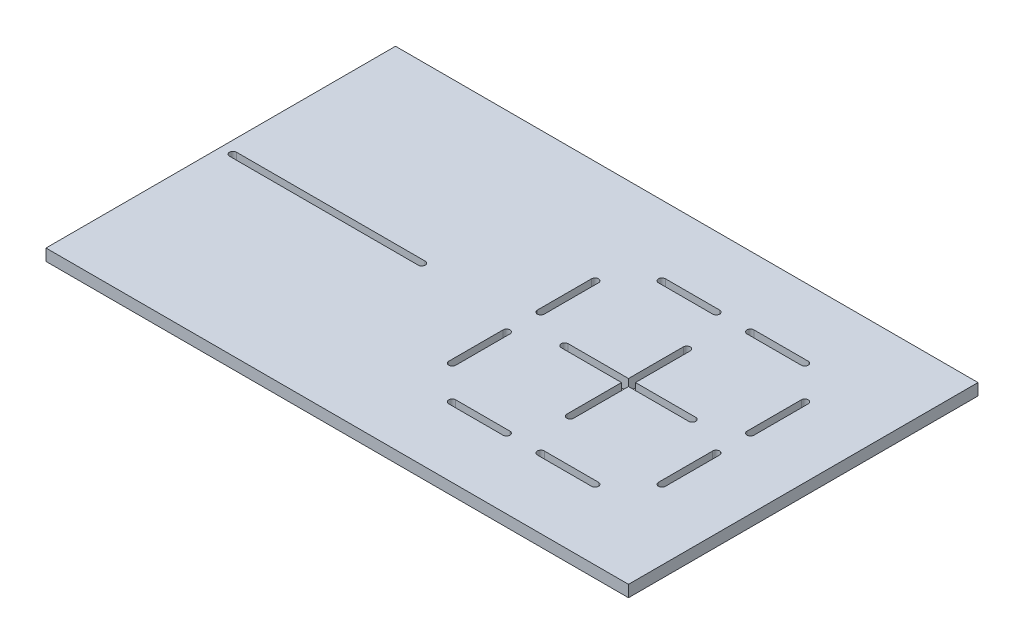
SolidWorks part; units mm, degrees
ref_plane "Front Plane" through (0, 0, 0) normal (0, 0, 1) x (1, 0, 0)
ref_plane "Top Plane" through (0, 0, 0) normal (0, 1, 0) x (1, 0, 0)
ref_plane "Right Plane" through (0, 0, 0) normal (1, 0, 0) x (0, 0, -1)
sketch "Sketch1" plane through (0, 0, 0) normal (0, 1, 0) x (1, 0, 0)
  line L1 (-54.3842, 257.5375) -> (445.6158, 257.5375)
  line L2 (-54.3842, 257.5375) -> (-54.3842, -42.4625)
  line L3 (-54.3842, -42.4625) -> (445.6158, -42.4625)
  line L4 (445.6158, 257.5375) -> (445.6158, -42.4625)
extrude "Boss-Extrude1" add sketch "Sketch1" along normal blind 10
sketch "Sketch2" plane through (0, 10, 0) normal (0, 1, 0) x (1, 0, 0)
  line L0 (-54.3842, 107.5375) -> (445.6158, 107.5375) construction
  line L1 (-54.3842, 257.5375) -> (-54.3842, -42.4625) construction
  line L2 (445.6158, -42.4625) -> (445.6158, 257.5375) construction
  line L3 (295.6158, 257.5375) -> (295.6158, -42.4625) construction
  line L4 (445.6158, 257.5375) -> (-54.3842, 257.5375) construction
  line L5 (-54.3842, -42.4625) -> (445.6158, -42.4625) construction
  line L6 (205.6158, 168.8297) -> (205.6158, 122.2426) construction
  line L7 (208.6158, 168.8297) -> (208.6158, 122.2426)
  line L8 (202.6158, 168.8297) -> (202.6158, 122.2426)
  line L9 (205.6158, 46.2453) -> (205.6158, 92.8323) construction
  line L10 (208.6158, 46.2453) -> (208.6158, 92.8323)
  line L11 (202.6158, 46.2453) -> (202.6158, 92.8323)
  line L12 (356.9081, 197.5375) -> (310.321, 197.5375) construction
  line L13 (356.9081, 194.5375) -> (310.321, 194.5375)
  line L14 (356.9081, 200.5375) -> (310.321, 200.5375)
  line L15 (234.3236, 197.5375) -> (280.9107, 197.5375) construction
  line L16 (234.3236, 194.5375) -> (280.9107, 194.5375)
  line L17 (234.3236, 200.5375) -> (280.9107, 200.5375)
  line L18 (385.6158, 46.2453) -> (385.6158, 92.8323) construction
  line L19 (382.6158, 46.2453) -> (382.6158, 92.8323)
  line L20 (388.6158, 46.2453) -> (388.6158, 92.8323)
  line L21 (385.6158, 168.8297) -> (385.6158, 122.2426) construction
  line L22 (382.6158, 168.8297) -> (382.6158, 122.2426)
  line L23 (388.6158, 168.8297) -> (388.6158, 122.2426)
  line L24 (234.3236, 17.5375) -> (280.9107, 17.5375) construction
  line L25 (234.3236, 20.5375) -> (280.9107, 20.5375)
  line L26 (234.3236, 14.5375) -> (280.9107, 14.5375)
  line L27 (356.9081, 17.5375) -> (310.321, 17.5375) construction
  line L28 (356.9081, 20.5375) -> (310.321, 20.5375)
  line L29 (356.9081, 14.5375) -> (310.321, 14.5375)
  arc A0 (208.6158, 168.8297) -> (202.6158, 168.8297) centre (205.6158, 168.8297) ccw
  arc A1 (202.6158, 122.2426) -> (208.6158, 122.2426) centre (205.6158, 122.2426) ccw
  arc A2 (208.6158, 46.2453) -> (202.6158, 46.2453) centre (205.6158, 46.2453) cw
  arc A3 (202.6158, 92.8323) -> (208.6158, 92.8323) centre (205.6158, 92.8323) cw
  arc A4 (356.9081, 194.5375) -> (356.9081, 200.5375) centre (356.9081, 197.5375) ccw
  arc A5 (310.321, 200.5375) -> (310.321, 194.5375) centre (310.321, 197.5375) ccw
  arc A6 (234.3236, 194.5375) -> (234.3236, 200.5375) centre (234.3236, 197.5375) cw
  arc A7 (280.9107, 200.5375) -> (280.9107, 194.5375) centre (280.9107, 197.5375) cw
  arc A8 (382.6158, 46.2453) -> (388.6158, 46.2453) centre (385.6158, 46.2453) ccw
  arc A9 (388.6158, 92.8323) -> (382.6158, 92.8323) centre (385.6158, 92.8323) ccw
  arc A10 (382.6158, 168.8297) -> (388.6158, 168.8297) centre (385.6158, 168.8297) cw
  arc A11 (388.6158, 122.2426) -> (382.6158, 122.2426) centre (385.6158, 122.2426) cw
  arc A12 (234.3236, 20.5375) -> (234.3236, 14.5375) centre (234.3236, 17.5375) ccw
  arc A13 (280.9107, 14.5375) -> (280.9107, 20.5375) centre (280.9107, 17.5375) ccw
  arc A14 (356.9081, 20.5375) -> (356.9081, 14.5375) centre (356.9081, 17.5375) cw
  arc A15 (310.321, 14.5375) -> (310.321, 20.5375) centre (310.321, 17.5375) cw
  point P14 (205.6158, 145.5362)
  point P22 (205.6158, 69.5388)
  point P31 (333.6145, 197.5375)
  point P38 (257.6172, 197.5375)
  point P45 (385.6158, 69.5388)
  point P52 (385.6158, 145.5362)
  point P59 (257.6172, 17.5375)
  point P66 (333.6145, 17.5375)
  point P71 (295.6158, 107.5375)
  dimension "D2" = 90
  dimension "D1" = 150
  dimension "D3" = 4
extrude "Cut-Extrude1" cut sketch "Sketch2" against normal blind 10
sketch "Sketch6" plane through (0, 10, 0) normal (0, 1, 0) x (1, 0, 0)
  line L0 (445.6158, 107.5375) -> (-54.3842, 107.5375) construction
  line L1 (445.6158, -42.4625) -> (445.6158, 257.5375) construction
  line L2 (-54.3842, 257.5375) -> (-54.3842, -42.4625) construction
  line L3 (295.6158, -42.4625) -> (295.6158, 257.5375) construction
  line L4 (-54.3842, -42.4625) -> (445.6158, -42.4625) construction
  line L5 (445.6158, 257.5375) -> (-54.3842, 257.5375) construction
  line L6 (-43.9007, 107.5375) -> (118.1126, 107.5375) construction
  line L7 (-43.9007, 110.5375) -> (118.1126, 110.5375)
  line L8 (-43.9007, 104.5375) -> (118.1126, 104.5375)
  arc A0 (-43.9007, 110.5375) -> (-43.9007, 104.5375) centre (-43.9007, 107.5375) ccw
  arc A1 (118.1126, 104.5375) -> (118.1126, 110.5375) centre (118.1126, 107.5375) ccw
  point P14 (37.1059, 107.5375)
  dimension "D1" = 150
extrude "Cut-Extrude2" cut sketch "Sketch6" against normal through all
sketch "Sketch7" plane through (0, 10, 0) normal (0, 1, 0) x (1, 0, 0)
  line L0 (-54.3842, 107.5375) -> (445.6158, 107.5375) construction
  line L1 (-54.3842, 257.5375) -> (-54.3842, -42.4625) construction
  line L2 (445.6158, -42.4625) -> (445.6158, 257.5375) construction
  line L3 (295.6158, 257.5375) -> (295.6158, -42.4625) construction
  line L4 (292.6158, 110.5375) -> (292.6158, 157.5375)
  line L5 (-54.3842, -42.4625) -> (445.6158, -42.4625) construction
  line L6 (445.6158, 257.5375) -> (-54.3842, 257.5375) construction
  line L7 (295.6158, 57.5375) -> (295.6158, 157.5375) construction
  line L8 (292.6158, 57.5375) -> (292.6158, 104.5375)
  line L9 (298.6158, 57.5375) -> (298.6158, 104.5375)
  line L10 (240.8754, 107.5375) -> (350.3563, 107.5375) construction
  line L11 (240.8754, 110.5375) -> (292.6158, 110.5375)
  line L12 (240.8754, 104.5375) -> (292.6158, 104.5375)
  line L13 (298.6158, 110.5375) -> (350.3563, 110.5375)
  line L14 (298.6158, 110.5375) -> (298.6158, 157.5375)
  line L15 (298.6158, 104.5375) -> (350.3563, 104.5375)
  arc A0 (292.6158, 57.5375) -> (298.6158, 57.5375) centre (295.6158, 57.5375) ccw
  arc A1 (298.6158, 157.5375) -> (292.6158, 157.5375) centre (295.6158, 157.5375) ccw
  arc A2 (240.8754, 110.5375) -> (240.8754, 104.5375) centre (240.8754, 107.5375) ccw
  arc A3 (350.3563, 104.5375) -> (350.3563, 110.5375) centre (350.3563, 107.5375) ccw
  point P8 (295.6158, 107.5375)
  point P21 (295.6158, 107.5375)
  point P26 (295.6158, 107.5375)
  point P27 (295.6158, 107.5375)
  point P28 (0, 0)
  point P29 (295.6158, 107.5375)
  dimension "D1" = 150
extrude "Cut-Extrude3" cut sketch "Sketch7" against normal through all
